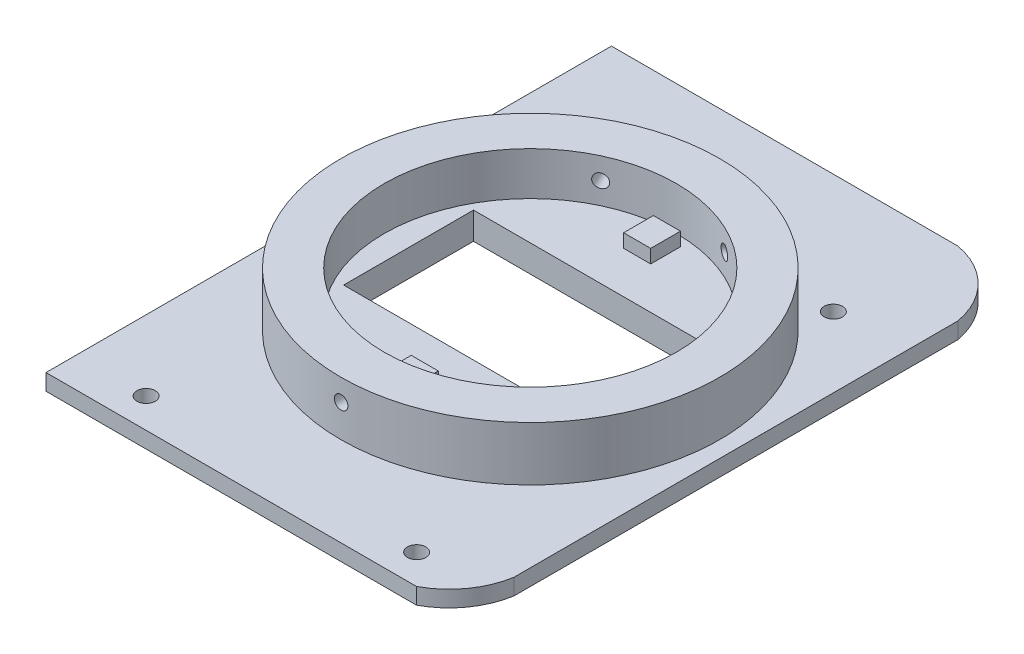
SolidWorks part; units mm, degrees
ref_plane "Front Plane" through (0, 0, 0) normal (0, 0, 1) x (1, 0, 0)
ref_plane "Top Plane" through (0, 0, 0) normal (0, 1, 0) x (1, 0, 0)
ref_plane "Right Plane" through (0, 0, 0) normal (1, 0, 0) x (0, 0, -1)
sketch "Sketch1" plane through (0, 0, 0) normal (0, 1, 0) x (1, 0, 0)
  line L1 (-30, 51) -> (30, 51)
  line L2 (-30, 51) -> (-30, -51)
  line L3 (-30, -51) -> (30, -51)
  line L4 (30, 51) -> (30, -51)
  line L5 (-30, 51) -> (30, -51) construction
  line L6 (-30, -51) -> (30, 51) construction
  point P0 (0, 0)
  dimension "D1" = 60
  dimension "D2" = 102
extrude "Boss-Extrude1" add sketch "Sketch1" along normal blind 3
hole_wizard "M3 Clearance Hole1" positions "3DSketch1" profile "Sketch3" hole size "M3" standard "ANSI Metric" end condition through all
sketch3d "3DSketch1"
  line L0 (-30, 3, -51) -> (-30, 3, 51) construction
  line L1 (30, 3, -51) -> (-30, 3, -51) construction
  line L2 (30, 3, 51) -> (30, 3, -51) construction
  point P0 (-25, 3, -36)
  point P2 (25, 3, -36)
  point P4 (-25, 3, 41)
  point P6 (25, 3, 41)
  dimension "D1" = 5
  dimension "D2" = 15
  dimension "D3" = 15
  dimension "D4" = 50
  dimension "D5" = 5
  dimension "D6" = 77
  dimension "D7" = 5
  dimension "D8" = 77
sketch "Sketch3" plane through (-25, 3, -36) normal (1, 0, 0) x (0, 0, 1)
  line L0 (0, 0) -> (0, 3)
  line L1 (0, 3) -> (1.7, 3)
  line L2 (1.7, 3) -> (1.7, 0)
  line L5 (1.7, 0) -> (0, 0)
  line L11 (0, -6.35) -> (0, 107.95) construction
  dimension "Thru Hole Dia." = 3.4
  dimension "Thru Hole Depth" = 3
sketch "Sketch5" plane through (0, 3, 0) normal (0, 1, 0) x (1, 0, 0)
  line L0 (30, 51) -> (-30, 51) construction
  line L1 (-30, 51) -> (-30, -51) construction
  circle A0 centre (0, 5) radius 35
  dimension "D3" = 70
  dimension "D1" = 46
  dimension "D2" = 30
extrude "Boss-Extrude2" add sketch "Sketch5" along normal blind 10
sketch "Sketch6" plane through (0, 13, 0) normal (0, 1, 0) x (1, 0, 0)
  line L0 (30, 51) -> (-30, 51) construction
  line L1 (-30, 51) -> (-30, 23.0278) construction
  circle A0 centre (0, 5) radius 27
  dimension "D3" = 54
  dimension "D1" = 46
  dimension "D2" = 30
extrude "Cut-Extrude1" cut sketch "Sketch6" against normal blind 8
sketch "Sketch8" plane through (0, 5, 0) normal (0, 1, 0) x (1, 0, 0)
  line L1 (-2.5, 30.25) -> (2.5, 30.25)
  line L2 (-2.5, 30.25) -> (-2.5, 24.75)
  line L3 (-2.5, 24.75) -> (2.5, 24.75)
  line L4 (2.5, 30.25) -> (2.5, 24.75)
  line L5 (-2.5, 30.25) -> (2.5, 24.75) construction
  line L6 (-2.5, 24.75) -> (2.5, 30.25) construction
  point P0 (0, 27.5)
  dimension "D1" = 5.5
  dimension "D2" = 5
  dimension "D3" = 0
  dimension "D4" = 27.5
extrude "Boss-Extrude3" add sketch "Sketch8" along normal blind 2.5
sketch "Sketch9" plane through (0, 5, 0) normal (0, 1, 0) x (1, 0, 0)
  line L1 (-2.5, -14.5) -> (2.5, -14.5)
  line L2 (-2.5, -14.5) -> (-2.5, -19.5)
  line L3 (-2.5, -19.5) -> (2.5, -19.5)
  line L4 (2.5, -14.5) -> (2.5, -19.5)
  line L5 (-2.5, -14.5) -> (2.5, -19.5) construction
  line L6 (-2.5, -19.5) -> (2.5, -14.5) construction
  point P0 (0, -17)
  dimension "D1" = 5
  dimension "D2" = 5
  dimension "D3" = 0
  dimension "D4" = 17
extrude "Boss-Extrude4" add sketch "Sketch9" along normal blind 2.5
sketch "Sketch10" plane through (0, 5, 0) normal (0, 1, 0) x (1, 0, 0)
  line L1 (-22.5, 17) -> (22.5, 17)
  line L2 (-22.5, 17) -> (-22.5, -7)
  line L3 (-22.5, -7) -> (22.5, -7)
  line L4 (22.5, 17) -> (22.5, -7)
  line L5 (-22.5, 17) -> (22.5, -7) construction
  line L6 (-22.5, -7) -> (22.5, 17) construction
  point P0 (0, 5)
  dimension "D1" = 5
  dimension "D2" = 45
  dimension "D3" = 24
extrude "Cut-Extrude2" cut sketch "Sketch10" against normal through all
sketch "Sketch12" plane through (0, 3, 0) normal (0, 1, 0) x (1, 0, 0)
  line L0 (-30, 51) -> (-30, 23.0278) construction
  line L1 (30, 51) -> (-30, 51)
  line L2 (30, 51) -> (30, 49)
  line L3 (30, 49) -> (-30, 49)
  line L4 (-30, 51) -> (-30, 49)
  dimension "D1" = 2
extrude "Cut-Extrude3" cut sketch "Sketch12" against normal through all
sketch "Sketch13" plane through (0, 3, 0) normal (0, 1, 0) x (1, 0, 0)
  line L0 (-30, 49) -> (-30, 23.0278) construction
  line L1 (30, -51) -> (-30, -51)
  line L2 (30, -51) -> (30, -48)
  line L3 (30, -48) -> (-30, -48)
  line L4 (-30, -51) -> (-30, -48)
  dimension "D1" = 3
extrude "Cut-Extrude4" cut sketch "Sketch13" against normal through all
sketch "Sketch14" plane through (0, 0, -49) normal (0, 0, -1) x (-1, 0, 0)
  line L1 (30, 3) -> (-30, 3)
  line L2 (30, 3) -> (30, 0)
  line L3 (30, 0) -> (-30, 0)
  line L4 (-30, 3) -> (-30, 0)
extrude "Boss-Extrude5" add sketch "Sketch14" along normal blind 9
sketch "Sketch16" plane through (-30, 0, 0) normal (-1, 0, 0) x (0, 0, 1)
  line L1 (-58, 0) -> (48, 0)
  line L2 (-58, 0) -> (-58, 3)
  line L3 (-58, 3) -> (48, 3)
  line L4 (48, 0) -> (48, 3)
extrude "Boss-Extrude6" add sketch "Sketch16" along normal blind 8
sketch "Sketch17" plane through (30, 0, 0) normal (1, 0, 0) x (0, 0, -1)
  line L1 (58, 3) -> (-48, 3)
  line L2 (58, 3) -> (58, 0)
  line L3 (58, 0) -> (-48, 0)
  line L4 (-48, 3) -> (-48, 0)
extrude "Boss-Extrude7" add sketch "Sketch17" along normal blind 8
sketch "Sketch18" plane through (0, 3, 0) normal (0, 1, 0) x (1, 0, 0)
  line L0 (38, 58) -> (38, -48) construction
  line L1 (-38, 58) -> (38, 58) construction
  line L2 (38, 46) -> (38, 58)
  line L3 (38, 58) -> (26, 58)
  arc A0 (38, 46) -> (26, 58) centre (23.389, 43.389) ccw
  dimension "D1" = 12
  dimension "D2" = 12
extrude "Cut-Extrude5" cut sketch "Sketch18" against normal blind 15
sketch "Sketch19" plane through (0, 3, 0) normal (0, 1, 0) x (1, 0, 0)
  line L0 (38, 46) -> (38, -48) construction
  line L1 (38, -48) -> (-38, -48) construction
  line L2 (38, -36) -> (38, -48)
  line L3 (38, -48) -> (26, -48)
  arc A0 (38, -36) -> (26, -48) centre (23.6646, -33.6646) cw
  dimension "D1" = 12
  dimension "D2" = 12
extrude "Cut-Extrude6" cut sketch "Sketch19" against normal through all
sketch "Sketch20" plane through (0, 3, 0) normal (0, 1, 0) x (1, 0, 0)
  line L0 (0, 58) -> (0, -48)
  line L1 (-38, 58) -> (26, 58) construction
  line L2 (26, -48) -> (-38, -48) construction
hole_wizard "M3x0.5 Tapped Hole1" positions "3DSketch2" profile "Sketch22" tap size "M3x0.5" standard "ANSI Metric" end condition up to next
sketch3d "3DSketch2"
  line L0 (0, 3, -58) -> (0, 3, 48) construction
  point P0 (-14.8324, 9, -36.7017)
  dimension "D1" = 6
  dimension "D2" = 16
sketch "Sketch22" plane through (-14.8324, 9, -36.7017) normal (0, 1, 0) x (-0.9058, 0, 0.4238)
  line L0 (0, 0) -> (0, 8)
  line L1 (0, 8) -> (1.25, 8)
  line L2 (1.25, 8) -> (1.25, 0)
  line L5 (1.25, 0) -> (0, 0)
  line L11 (0, -6.35) -> (0, 107.95) construction
  dimension "Thread Major Dia." = 2.5
  dimension "Thru Tap Drill Depth" = 8
hole_wizard "M3x0.5 Tapped Hole2" positions "3DSketch3" profile "Sketch23" tap size "M3x0.5" standard "ANSI Metric" end condition up to next
sketch3d "3DSketch3"
  line L0 (0, 3, -58) -> (0, 3, 48) construction
  point P0 (14.8324, 9, -36.7017)
  dimension "D1" = 6
  dimension "D2" = 16
sketch "Sketch23" plane through (14.8324, 9, -36.7017) normal (0, 1, 0) x (-0.9058, 0, -0.4238)
  line L0 (0, 0) -> (0, 8)
  line L1 (0, 8) -> (1.25, 8)
  line L2 (1.25, 8) -> (1.25, 0)
  line L5 (1.25, 0) -> (0, 0)
  line L11 (0, -6.35) -> (0, 107.95) construction
  dimension "Thread Major Dia." = 2.5
  dimension "Thru Tap Drill Depth" = 8
hole_wizard "M3x0.5 Tapped Hole3" positions "3DSketch7" profile "Sketch27" tap size "M3x0.5" standard "ANSI Metric" end condition up to next
sketch3d "3DSketch7"
  point P0 (0.02, 9, 30)
  dimension "D1" = 6
  dimension "D2" = 38.02
sketch "Sketch27" plane through (0.02, 9, 30) normal (0, 1, 0) x (1, 0, -0.0006)
  line L0 (0, 0) -> (0, 8)
  line L1 (0, 8) -> (1.25, 8)
  line L2 (1.25, 8) -> (1.25, 0)
  line L5 (1.25, 0) -> (0, 0)
  line L11 (0, -6.35) -> (0, 107.95) construction
  dimension "Thread Major Dia." = 2.5
  dimension "Thru Tap Drill Depth" = 8
sketch "Sketch28" plane through (0, 3, 0) normal (0, 1, 0) x (1, 0, 0)
  line L1 (-38, -48) -> (38, -48)
  line L2 (-38, -48) -> (-38, -46.5)
  line L3 (-38, -46.5) -> (38, -46.5)
  line L4 (38, -48) -> (38, -46.5)
  dimension "D1" = 1.5
extrude "Cut-Extrude7" cut sketch "Sketch28" against normal through all
sketch "Sketch29" plane through (0, 0, 0) normal (0, -1, 0) x (1, 0, 0)
  line L0 (0, 46.414) -> (0, -51.2556)
  line L1 (0, -58) -> (0, 48) construction
  line L2 (-32.3165, -5) -> (32.6058, -5)
